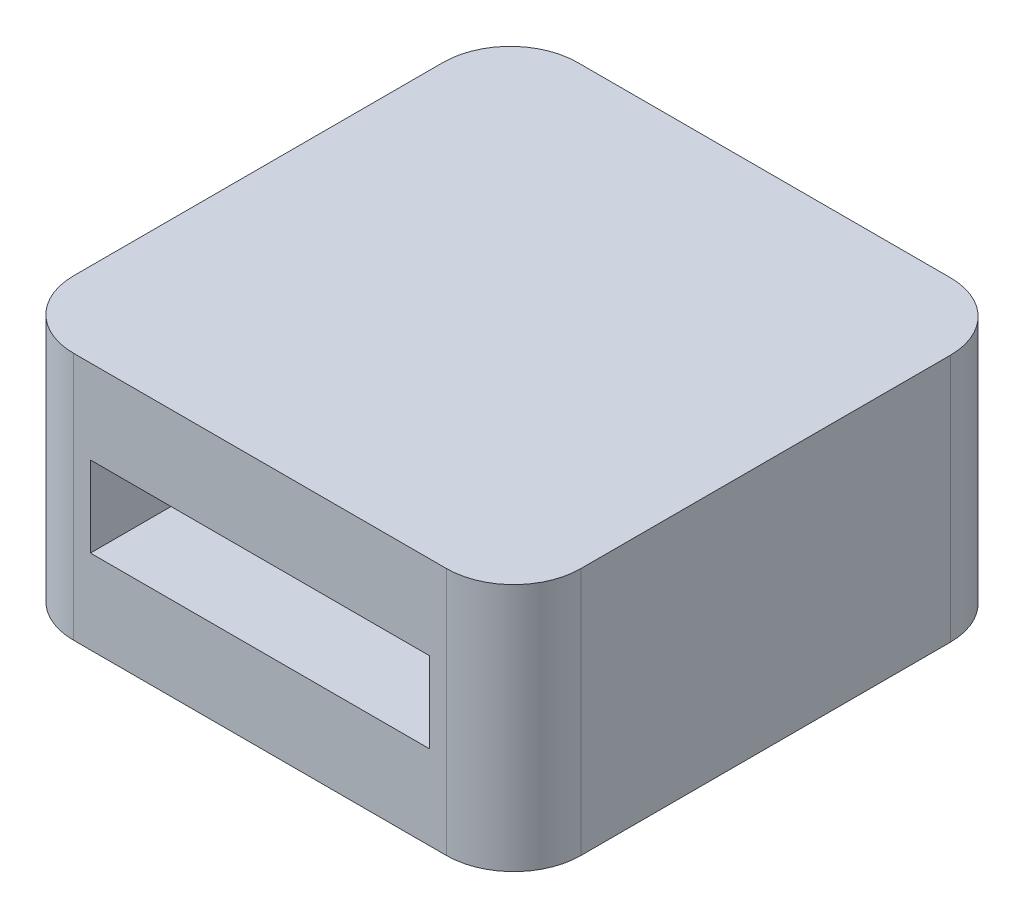
SolidWorks part; units mm, degrees
ref_plane "Front Plane" through (0, 0, 0) normal (0, 0, 1) x (1, 0, 0)
ref_plane "Top Plane" through (0, 0, 0) normal (0, 1, 0) x (1, 0, 0)
ref_plane "Right Plane" through (0, 0, 0) normal (1, 0, 0) x (0, 0, -1)
sketch "Profile Sketch" plane through (0, 0, 0) normal (0, 0, 1) x (1, 0, 0)
  line L0 (0, 1.2) -> (0, 3.7) construction
  line L1 (-5.05, -1.2) -> (5.05, -1.2)
  line L2 (-5.05, -1.2) -> (-5.05, 1.2)
  line L3 (-5.05, 1.2) -> (5.05, 1.2)
  line L4 (5.05, -1.2) -> (5.05, 1.2)
  line L5 (-5.05, -1.2) -> (5.05, 1.2) construction
  line L6 (-5.05, 1.2) -> (5.05, -1.2) construction
  line L7 (-7.55, -3.7) -> (7.55, -3.7)
  line L8 (-7.55, -3.7) -> (-7.55, 3.7)
  line L9 (-7.55, 3.7) -> (7.55, 3.7)
  line L10 (7.55, -3.7) -> (7.55, 3.7)
  line L11 (-7.55, -3.7) -> (7.55, 3.7) construction
  line L12 (-7.55, 3.7) -> (7.55, -3.7) construction
  line L13 (-5.05, 0) -> (-7.55, 0) construction
  point P0 (0, 0)
  point P6 (0, 0)
  dimension "D1" = 10.1
  dimension "D2" = 2.5
  dimension "D3" = 2.4
extrude "Profile Extrude" add sketch "Profile Sketch" along normal blind 15
fillet "Corner Fillets" radius 2 4 edges at (-7.55, 0, 0) (7.55, 0, 0) (7.55, 0, 15) (-7.55, 0, 15)
